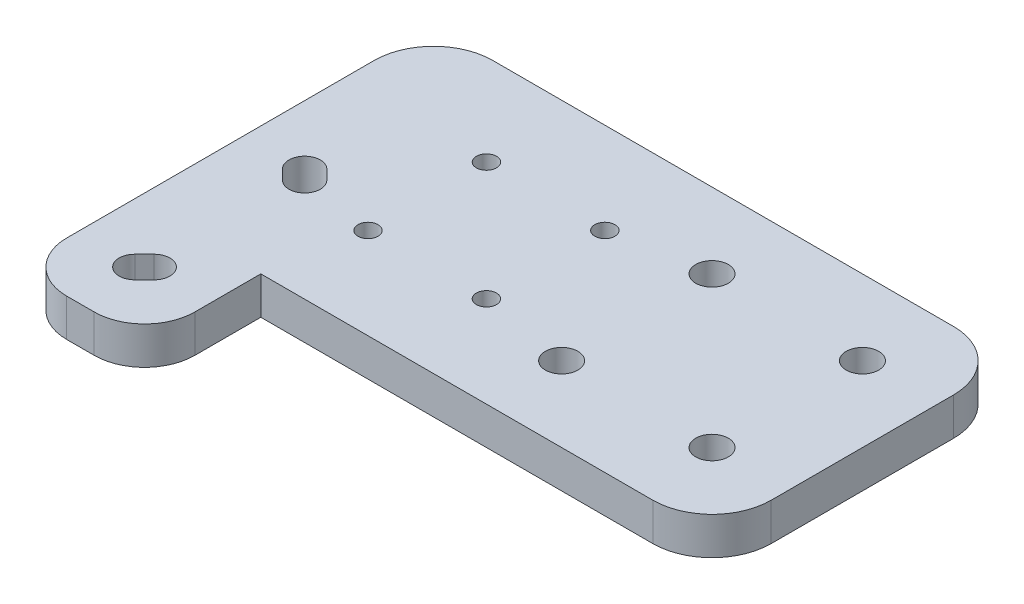
SolidWorks part; units mm, degrees
material "6061-T6 (SS)"
ref_plane "Front" through (0, 0, 0) normal (0, 0, 1) x (1, 0, 0)
ref_plane "Top" through (0, 0, 0) normal (0, 1, 0) x (1, 0, 0)
ref_plane "Right" through (0, 0, 0) normal (1, 0, 0) x (0, 0, -1)
sketch "Sketch1" plane through (0, 0, 0) normal (0, 1, 0) x (1, 0, 0)
  line L0 (-12.7, 25.4) -> (-12.7, -25.4) construction
  line L1 (38.1, -25.4) -> (-38.1, -25.4)
  line L2 (38.1, -25.4) -> (38.1, 25.4)
  line L3 (38.1, 25.4) -> (-38.1, 25.4)
  line L4 (-38.1, -25.4) -> (-38.1, 25.4) construction
  line L5 (38.1, -25.4) -> (-38.1, 25.4) construction
  line L6 (38.1, 25.4) -> (-38.1, -25.4) construction
  line L7 (25.4, -25.4) -> (25.4, 25.4) construction
  line L8 (0, 25.4) -> (0, -25.4) construction
  line L9 (38.1, 0) -> (-38.1, 0) construction
  line L10 (-12.7, 0) -> (-38.1, 0) construction
  line L11 (0, 0) -> (0, 25.4) construction
  line L12 (0, 12.7) -> (38.1, 12.7) construction
  line L13 (-25.4, 0) -> (-25.4, 25.4) construction
  line L14 (-15.4, 10) -> (-35.4, 10) construction
  line L15 (-38.1, 25.4) -> (-59.74, 25.4)
  line L16 (-59.74, 25.4) -> (-59.74, -45.04)
  line L17 (-59.74, -45.04) -> (-38.1, -45.04)
  line L18 (-38.1, -45.04) -> (-38.1, -25.4)
  line L19 (-38.1, 0) -> (-49.74, 0) construction
  line L20 (-49.74, -41.4) -> (-2.5231, -41.4) construction
  line L21 (-49.74, -35.04) -> (-49.74, -45.04) construction
  line L22 (-49.74, -6.36) -> (-49.74, -35.04) construction
  line L23 (-49.74, -6.36) -> (-59.74, -6.36) construction
  line L24 (-49.74, -6.36) -> (-49.74, -8.86) construction
  line L25 (-56.1, -6.36) -> (-56.1, -8) construction
  line L26 (-49.74, -6.36) -> (-48.1, -8) construction
  line L27 (-56.1, -6.36) -> (-56.1, -35.04) construction
  line L28 (-49.74, -35.04) -> (-48.1, -33.4) construction
  line L29 (-15.4, 12.5) -> (-35.4, 12.5) construction
  line L30 (-35.4, 12.5) -> (-35.4, 10) construction
  circle A0 centre (-15.4, 10) radius 1.5 construction
  circle A1 centre (-35.4, 10) radius 1.5 construction
  circle A2 centre (-35.4, -10) radius 1.5 construction
  circle A3 centre (-15.4, -10) radius 1.5 construction
  circle A4 centre (0, 12.7) radius 2.5 construction
  circle A5 centre (25.4, 12.7) radius 2.5 construction
  circle A6 centre (25.4, -12.7) radius 2.5 construction
  circle A7 centre (0, -12.7) radius 2.5 construction
  circle A8 centre (-49.74, -6.36) radius 6.36 construction
  circle A9 centre (-49.74, -35.04) radius 6.36 construction
  circle A10 centre (-49.74, -6.36) radius 10 construction
  circle A11 centre (-49.74, -35.04) radius 10 construction
  circle A12 centre (-49.74, -6.36) radius 2.5 construction
  circle A13 centre (-49.74, -35.04) radius 2.5 construction
  circle A14 centre (-48.1, -8) radius 8 construction
  circle A15 centre (-48.1, -8) radius 10 construction
  circle A16 centre (-48.1, -33.4) radius 8 construction
  point P0 (0, 0)
  point P23 (-25.4, 10)
  point P64 (-25.4, 12.5)
  dimension "D8" = 3
  dimension "D9" = 5
  dimension "D10" = 12.72
  dimension "D11" = 5
  dimension "D12" = 20
  dimension "D14" = 16
  dimension "D15" = 12.5
  dimension "D1" = 50.8
  dimension "D2" = 76.2
  dimension "D3" = 12.7
  dimension "D4" = 25.4
  dimension "D5" = 25.4
  dimension "D6" = 10
  dimension "D7" = 20
  dimension "D13" = 16
extrude "Boss-Extrude1" add sketch "Sketch1" along normal blind 6.35
fillet "Fillet1" radius 8.5 2 edges at (-59.74, 3.175, 45.04) (-38.1, 3.175, 45.04)
fillet "Fillet2" radius 10 3 edges at (38.1, 3.175, -25.4) (38.1, 3.175, 25.4) (-59.74, 3.175, -25.4)
hole_wizard "M5 Clearance Hole1" positions "Sketch3" profile "Sketch2" hole size "M5" standard "ISO" end condition through all
sketch "Sketch3" plane through (0, 6.35, 0) normal (0, 1, 0) x (-1, 0, 0)
  point P6 (0, 12.7)
  point P9 (-25.4, 12.7)
  point P12 (-25.4, -12.7)
  point P15 (0, -12.7)
sketch "Sketch2" plane through (0, 6.35, 12.7) normal (1, 0, 0) x (0, 0, 1)
  line L0 (0, 0) -> (0, 6.35)
  line L1 (0, 6.35) -> (2.75, 6.35)
  line L2 (2.75, 6.35) -> (2.75, 0)
  line L5 (2.75, 0) -> (0, 0)
  line L11 (0, -6.35) -> (0, 107.95) construction
  dimension "Thru Hole Dia." = 5.5
  dimension "Thru Hole Depth" = 6.35
hole_wizard "M3 Clearance Hole1" positions "Sketch5" profile "Sketch4" hole size "M3" standard "ISO" end condition through all
sketch "Sketch5" plane through (0, 6.35, 0) normal (0, 1, 0) x (-1, 0, 0)
  point P0 (15.4, 10)
  point P3 (15.4, -10)
  point P6 (35.4, -10)
  point P9 (35.4, 10)
sketch "Sketch4" plane through (-15.4, 6.35, 10) normal (1, 0, 0) x (0, 0, 1)
  line L0 (0, 0) -> (0, 6.35)
  line L1 (0, 6.35) -> (1.7, 6.35)
  line L2 (1.7, 6.35) -> (1.7, 0)
  line L5 (1.7, 0) -> (0, 0)
  line L11 (0, -6.35) -> (0, 107.95) construction
  dimension "Thru Hole Dia." = 3.4
  dimension "Thru Hole Depth" = 6.35
sketch "Sketch8" plane through (0, 6.35, 0) normal (0, 1, 0) x (1, 0, 0)
  line L0 (-49.74, -6.36) -> (-48.1, -8) construction
  line L1 (-51.6138, -8.2338) -> (-49.9738, -9.8738)
  line L2 (-47.8662, -4.4862) -> (-46.2262, -6.1262)
  line L3 (-49.74, -35.04) -> (-48.1, -33.4) construction
  line L4 (-47.8662, -36.9138) -> (-46.2262, -35.2738)
  line L5 (-51.6138, -33.1662) -> (-49.9738, -31.5262)
  arc A0 (-51.6138, -8.2338) -> (-47.8662, -4.4862) centre (-49.74, -6.36) cw
  arc A1 (-49.9738, -9.8738) -> (-46.2262, -6.1262) centre (-48.1, -8) ccw
  arc A2 (-47.8662, -36.9138) -> (-51.6138, -33.1662) centre (-49.74, -35.04) cw
  arc A3 (-46.2262, -35.2738) -> (-49.9738, -31.5262) centre (-48.1, -33.4) ccw
  dimension "D1" = 2.65
  dimension "D2" = 2.65
  dimension "D3" = 2.65
  dimension "D4" = 2.65
extrude "Cut-Extrude1" cut sketch "Sketch8" against normal through all
